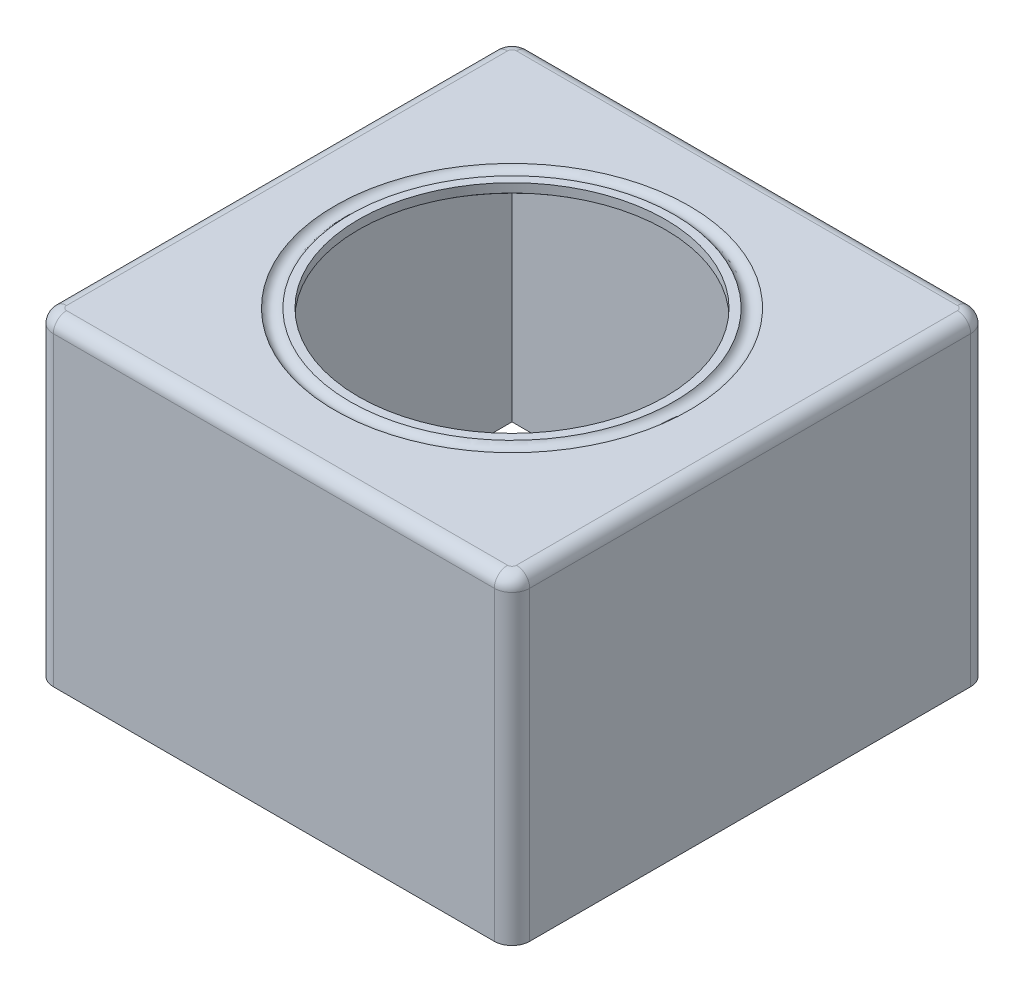
SolidWorks part; units mm, degrees
ref_plane "Front Plane" through (0, 0, 0) normal (0, 0, 1) x (1, 0, 0)
ref_plane "Top Plane" through (0, 0, 0) normal (0, 1, 0) x (1, 0, 0)
ref_plane "Right Plane" through (0, 0, 0) normal (1, 0, 0) x (0, 0, -1)
sketch "Sketch1" plane through (0, 0, 0) normal (0, 1, 0) x (1, 0, 0)
  line L1 (-49.7519, -53.7519) -> (49.7519, -53.7519)
  line L2 (-53.7519, -49.7519) -> (-53.7519, 49.7519)
  line L3 (-49.7519, 53.7519) -> (49.7519, 53.7519)
  line L4 (53.7519, -49.7519) -> (53.7519, 49.7519)
  line L5 (-53.7519, -53.7519) -> (53.7519, 53.7519) construction
  line L6 (-53.7519, 53.7519) -> (53.7519, -53.7519) construction
  line L11 (-49.7519, -49.7519) -> (49.7519, -49.7519)
  line L12 (-49.7519, -49.7519) -> (-49.7519, 49.7519)
  line L13 (-49.7519, 49.7519) -> (49.7519, 49.7519)
  line L14 (49.7519, -49.7519) -> (49.7519, 49.7519)
  line L15 (-49.7519, -49.7519) -> (49.7519, 49.7519) construction
  line L16 (-49.7519, 49.7519) -> (49.7519, -49.7519) construction
  arc A0 (-49.7519, -53.7519) -> (-53.7519, -49.7519) centre (-49.7519, -49.7519) cw
  arc A1 (49.7519, -53.7519) -> (53.7519, -49.7519) centre (49.7519, -49.7519) ccw
  arc A2 (49.7519, 53.7519) -> (53.7519, 49.7519) centre (49.7519, 49.7519) cw
  arc A3 (-53.7519, 49.7519) -> (-49.7519, 53.7519) centre (-49.7519, 49.7519) cw
  point P0 (0, 0)
  point P18 (0, 0)
  dimension "D1" = 4
extrude "Boss-Extrude1" add sketch "Sketch1" along normal blind 70
sketch "Sketch2" plane through (0, 70, 0) normal (0, 1, 0) x (1, 0, 0)
  line L0 (49.7519, 53.7519) -> (-49.7519, 53.7519) construction
  line L1 (53.7519, -53.7519) -> (-53.7519, -53.7519)
  line L2 (53.7519, -53.7519) -> (53.7519, 53.7519)
  line L3 (53.7519, 53.7519) -> (-53.7519, 53.7519)
  line L4 (-53.7519, -53.7519) -> (-53.7519, 53.7519)
  line L5 (53.7519, -53.7519) -> (-53.7519, 53.7519) construction
  line L6 (53.7519, 53.7519) -> (-53.7519, -53.7519) construction
  line L7 (-53.7519, 49.7519) -> (-53.7519, -49.7519) construction
  circle A2 centre (0, 0) radius 41.0551
  point P0 (0, 0)
  arc M3 (-53.7519, -49.7519) -> (-49.7519, -53.7519) centre (-49.7519, -49.7519) ccw
  line M4 (-49.7519, -53.7519) -> (49.7519, -53.7519)
  arc M5 (49.7519, -53.7519) -> (53.7519, -49.7519) centre (49.7519, -49.7519) ccw
  line M6 (53.7519, -49.7519) -> (53.7519, 49.7519)
  arc M7 (53.7519, 49.7519) -> (49.7519, 53.7519) centre (49.7519, 49.7519) ccw
  line M8 (49.7519, 53.7519) -> (-49.7519, 53.7519)
  arc M9 (-49.7519, 53.7519) -> (-53.7519, 49.7519) centre (-49.7519, 49.7519) ccw
  line M10 (-53.7519, 49.7519) -> (-53.7519, -49.7519)
  line M11 (-49.7519, -49.7519) -> (-49.7519, 49.7519)
  line M12 (-49.7519, 49.7519) -> (49.7519, 49.7519)
  line M13 (49.7519, 49.7519) -> (49.7519, -49.7519)
  line M14 (49.7519, -49.7519) -> (-49.7519, -49.7519)
extrude "Boss-Extrude2" add sketch "Sketch2" along normal blind 2 contours M10 M3 M4 M5 M6 M7 M8 M9 M14 M11 M12 M13 | A2 M11 M14 M13 M12 region at (0, 70, 52.2316) region at (-48.3447, 70, 0)
fillet "Fillet1" radius 3 8 edges at (52.5804, 72, 52.5804) (0, 72, 53.7519) (-52.5804, 72, 52.5804) (-53.7519, 72, 0) (-52.5804, 72, -52.5804) (0, 72, -53.7519) (52.5804, 72, -52.5804) (53.7519, 72, 0)
sketch "Sketch6" plane through (0, 0, 0) normal (1, 0, 0) x (0, 0, -1)
  line L0 (0, 0) -> (0, 101.2954) construction
  line L1 (-41.9063, 70) -> (0, 70) construction
  line L2 (49.7519, 70) -> (-49.7519, 70) construction
  line L3 (41.0551, 72) -> (-41.0551, 72) construction
  line L4 (-41.9063, 70) -> (-41.9063, 72)
  line L5 (49.7519, 72) -> (-49.7519, 72) construction
  line L6 (-39.9779, 72) -> (-41.9063, 72)
  line L7 (-36.5598, 72) -> (-34.6314, 72)
  line L8 (-34.6314, 72) -> (-34.6314, 70)
  arc A0 (-39.9779, 72) -> (-36.5598, 72) centre (-38.2688, 72.9882) ccw
  arc A1 (-41.9063, 70) -> (-34.6314, 70) centre (-38.2688, 74.2066) ccw
  point P16 (-40.4119, 72)
revolve "Revolve1" add sketch "Sketch6" angle 360 about L0
